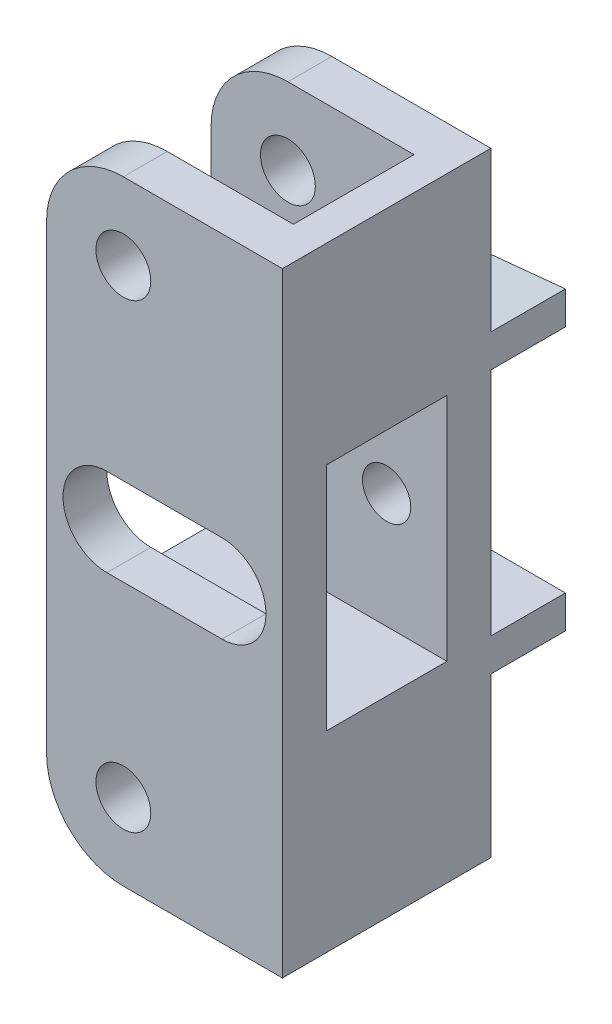
SolidWorks part; units mm, degrees
ref_plane "前视基准面" through (0, 0, 0) normal (0, 0, 1) x (1, 0, 0)
ref_plane "上视基准面" through (0, 0, 0) normal (0, 1, 0) x (1, 0, 0)
ref_plane "右视基准面" through (0, 0, 0) normal (1, 0, 0) x (0, 0, -1)
sketch "草图1" plane through (0, 0, 0) normal (0, 0, 1) x (1, 0, 0)
  line L0 (-612.4365, 0) -> (30009.3904, 0) construction
  line L1 (-611.4109, 10) -> (30010.416, 10) construction
  line L2 (-607.9921, -10) -> (30013.8348, -10) construction
  line L3 (0, -612.4365) -> (0, 30009.3904) construction
  line L4 (-10, -612.4365) -> (-10, 30009.3904) construction
  line L5 (10, -614.6741) -> (10, 30007.1528) construction
  line L6 (-37, -1047.5802) -> (-37, 48952.4198) construction
  line L7 (-1052.765, 15) -> (48947.235, 15) construction
  line L8 (-50, 21) -> (-50, -21)
  line L9 (-50, 10.5) -> (-28.5, 10.5)
  line L10 (-44.5, 0) -> (-34, 0) construction
  line L11 (-11, -31.9293) -> (-11, 31.9293) construction
  line L12 (-31, -1000) -> (-31, 49000) construction
  line L13 (-25, -1048.411) -> (-25, 48951.589) construction
  line L14 (-43, 28) -> (-28.5, 28)
  line L15 (-43, 12.1) -> (-50, 12.1)
  line L16 (-34.5021, 18.3549) -> (-31.5, 28)
  line L17 (-28.5, 28) -> (-28.5, 10.5)
  line L18 (-28.5, 10.5) -> (-28.5, -10.5)
  line L19 (-28.5, -28) -> (-28.5, -10.5)
  line L20 (-34.5021, -18.3549) -> (-31.5, -28)
  line L21 (-43, -12.1) -> (-50, -12.1)
  line L22 (-43, -28) -> (-28.5, -28)
  line L23 (-50, -10.5) -> (-28.5, -10.5)
  line L24 (-44.5, 4) -> (-34, 4)
  line L25 (-44.5, -4) -> (-34, -4)
  line L26 (-42.118, 12.1438) -> (-28.5, 13.5)
  line L27 (-42.118, -12.1438) -> (-28.5, -13.5)
  circle A0 centre (-43, 21) radius 6 construction
  circle A1 centre (-43, 21) radius 7
  circle A2 centre (-43, 21) radius 2.5
  arc A3 (-43, 12.1) -> (-34.5021, 18.3549) centre (-43, 21) ccw
  circle A4 centre (-44.5, 0) radius 2.2
  circle A5 centre (-43, -21) radius 6 construction
  arc A6 (-43, -12.1) -> (-34.5021, -18.3549) centre (-43, -21) cw
  circle A7 centre (-43, -21) radius 2.5
  circle A12 centre (-43, -21) radius 7
  circle A13 centre (-34, 0) radius 2.2
  arc A14 (-44.5, 4) -> (-44.5, -4) centre (-44.5, 0) ccw
  arc A15 (-34, -4) -> (-34, 4) centre (-34, 0) ccw
  point P47 (-39.25, 0)
  point P50 (-28.5, 0)
  point P56 (-50, 0)
  dimension "D5" = 12
  dimension "D6" = 14
  dimension "D7" = 5
  dimension "D9" = 5
  dimension "D10" = 1.6
  dimension "D11" = 10.5
  dimension "D12" = 3
  dimension "D8" = 12
  dimension "D18" = 4.4
  dimension "D19" = 3.5
  dimension "D21" = 10.5
  dimension "D25" = 40
  dimension "D20" = 4
  dimension "D1" = 20
  dimension "D2" = 10
  dimension "D3" = 20
  dimension "D4" = 10
  dimension "D13" = 8.9
  dimension "D14" = 6
  dimension "D15" = 5.5
  dimension "D16" = 21
  dimension "D17" = 5.5
  dimension "D22" = 3
  dimension "D23" = 18.5
  dimension "D24" = 1
extrude "凸台-拉伸1" add sketch "草图1" along normal blind 4 contours L15 A3 L16 L14 A1 L8 | A1 A2 | A3 L15 L8 L9 L17 L14 L16 | L8 L23 L18 L9 A15 L25 A14 L24 | L21 A6 L20 L22 L19 L23 L8 | L8 A12 L22 L20 A6 L21 | A12 A7 | A3 L26 L17 L14 L16 | L27 A6 L20 L22 L19 region at (-43, 13.7561, 0) region at (-47.8097, 25.8097, 0) region at (-37.9015, 11.5818, 0) region at (-39.25, 10.1995, 0) region at (-31.7873, 19.0677, 0) region at (-37.9015, -11.5818, 0) region at (-46.5, -12.3439, 0) region at (-43, -14.198, 0) region at (-31.7873, -19.0677, 0)
extrude "凸台-拉伸2" add sketch "草图1<5>" against normal blind 11 contours A3 L15 L8 L9 L17 L14 L16 | L21 A6 L20 L22 L19 L23 L8 | A3 L26 L17 L14 L16 | L27 A6 L20 L22 L19 region at (-37.9015, 11.5818, 0) region at (-31.7873, 19.0677, 0) region at (-37.9015, -11.5818, 0) region at (-31.7873, -19.0677, 0)
sketch "草图1<5>" plane through (0, 0, 0) normal (0, 0, 1) x (1, 0, 0) same geometry as "草图1"
extrude "凸台-拉伸3" add sketch "草图1<6>" against normal blind 4 from vertex contours L15 A3 L16 L14 A1 L8 | A3 L15 L8 L9 L17 L14 L16 | A1 A2 | L8 L23 L18 L9 A15 L25 A14 L24 | L25 A15 L24 A14 A4 A13 | L21 A6 L20 L22 L19 L23 L8 | L8 A12 L22 L20 A6 L21 | A12 A7 | A3 L26 L17 L14 L16 | L27 A6 L20 L22 L19 region at (-43, 13.7561, 0) region at (-47.8097, 25.8097, 0) region at (-37.9015, 11.5818, 0) region at (-39.25, 10.1995, 0) region at (-31.7873, 19.0677, 0) region at (-37.9015, -11.5818, 0) region at (-46.5, -12.3439, 0) region at (-43, -14.198, 0) region at (-31.7873, -19.0677, 0) region at (-39.25, 0, 0) starting at point (-28.5, 28, -11)
sketch "草图1<6>" plane through (0, 0, 0) normal (0, 0, 1) x (1, 0, 0) same geometry as "草图1"
extrude "凸台-拉伸4" add sketch "草图1<7>" against normal blind 6.8 from vertex contours A3 L15 L8 L9 L17 L26 | L21 A6 L27 L19 L23 L8 region at (-37.9015, 11.5818, 0) region at (-37.9015, -11.5818, 0) starting at point (-50, -21, -15)
sketch "草图1<7>" plane through (0, 0, 0) normal (0, 0, 1) x (1, 0, 0) same geometry as "草图1"
fillet "圆角1" radius 5 2 edges at (-50, 11.3, -21.8) (-50, -11.3, -21.8)
